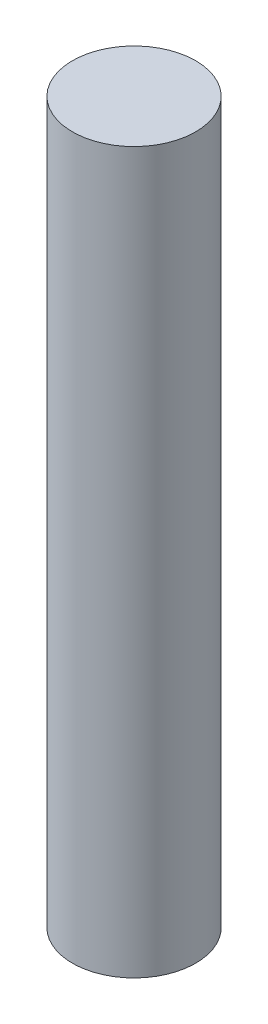
SolidWorks part; units mm, degrees
material "ABS PC"
ref_plane "Front Plane" through (0, 0, 0) normal (0, 0, 1) x (1, 0, 0)
ref_plane "Top Plane" through (0, 0, 0) normal (0, 1, 0) x (1, 0, 0)
ref_plane "Right Plane" through (0, 0, 0) normal (1, 0, 0) x (0, 0, -1)
sketch "Sketch1" plane through (0, 0, 0) normal (0, 1, 0) x (1, 0, 0)
  circle A0 centre (0, 0) radius 2.5
  dimension "D1" = 5
extrude "Boss-Extrude1" add sketch "Sketch1" along normal blind 29.21
